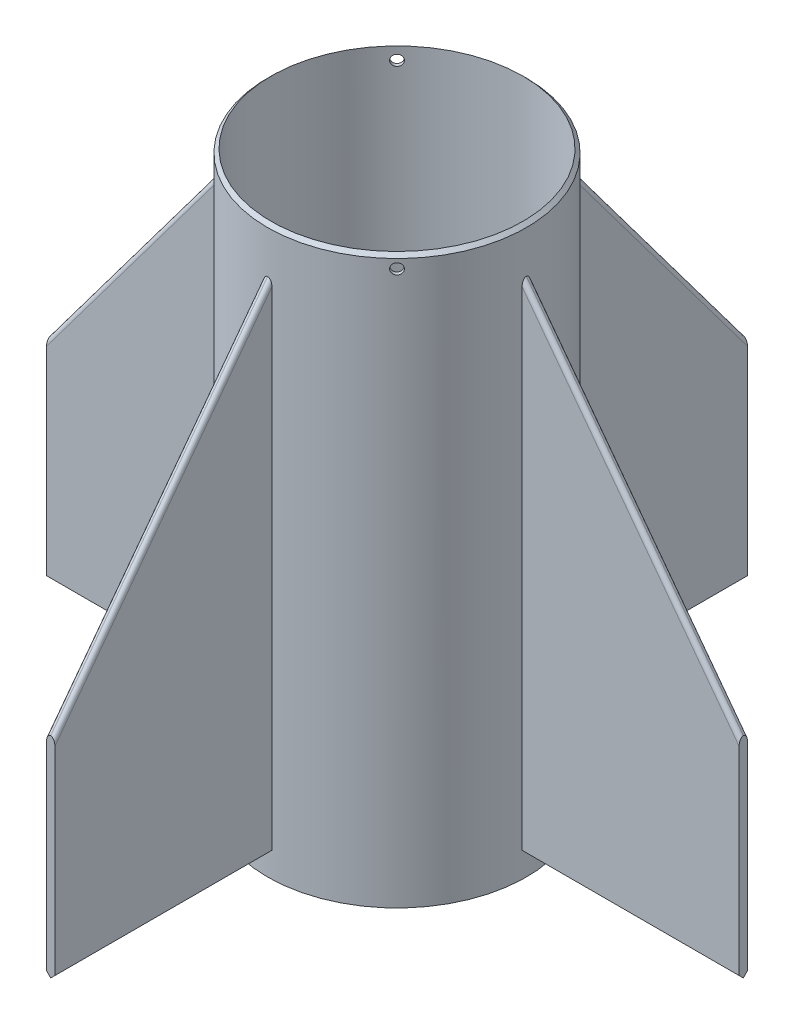
SolidWorks part; units mm, degrees
material "Thornel VCB-20 Carbon Cloth"
ref_plane "Front Plane" through (0, 0, 0) normal (0, 0, 1) x (1, 0, 0)
ref_plane "Top Plane" through (0, 0, 0) normal (0, 1, 0) x (1, 0, 0)
ref_plane "Right Plane" through (0, 0, 0) normal (1, 0, 0) x (0, 0, -1)
sketch "Sketch1" plane through (0, 0, 0) normal (0, 1, 0) x (1, 0, 0)
  circle A0 centre (0, 0) radius 76.2
  circle A1 centre (0, 0) radius 78.359
  dimension "D1" = 152.4
  dimension "D2" = 156.718
extrude "Boss-Extrude1" add sketch "Sketch1" along normal blind 342.9
sketch "Sketch2" plane through (0, 0, 0) normal (0, 0, 1) x (1, 0, 0)
  line L0 (76.2, 317.5) -> (76.2, 12.7)
  line L1 (76.2, 12.7) -> (209.55, 12.7)
  line L2 (209.55, 12.7) -> (209.55, 139.7)
  line L3 (209.55, 139.7) -> (76.2, 317.5)
  dimension "D1" = 76.2
  dimension "D2" = 127
  dimension "D3" = 133.35
  dimension "D4" = 304.8
  dimension "D5" = 177.8
  dimension "D6" = 12.7
extrude "Boss-Extrude2" add sketch "Sketch2" along normal blind 2.54 and the other way blind 2.54 separate body
sketch "Sketch3" plane through (0, 0, 0) normal (0, 0, 1) x (1, 0, 0)
  line L0 (0, -69.284) -> (0, 493.4849) construction
fillet "Fillet2" radius 2.54 2 edges at (142.875, 228.6, -2.54) (142.875, 228.6, 2.54)
chamfer "Chamfer2" distance 2.54 angle 45 2 edges at (142.875, 12.7, -2.54) (142.875, 12.7, 2.54)
pattern_circular "CirPattern1" count 4 over 360 about axis through (0, -69.284, 0) along (0, 1, 0) of bodies 102
ref_plane "Plane1" through (0, 0, 0) normal (-0.7071, 0, -0.7071) x (-0.7071, 0, 0.7071)
sketch "Sketch4" plane through (0, 0, 0) normal (-0.7071, 0, -0.7071) x (-0.7071, 0, 0.7071)
  line L0 (0, 342.9) -> (0, 0) construction
  circle A0 centre (0, 334.9498) radius 3.175
  dimension "D1" = 6.35
  dimension "D2" = 334.9498
extrude "Cut-Extrude1" cut sketch "Sketch4" against normal through all contours A0
pattern_circular "CirPattern2" count 4 over 360 about axis through (0, -69.284, 0) along (0, 1, 0) of "Cut-Extrude1" reverse direction yes
chamfer "Chamfer3" distance 2.54 angle 45 1 edges at (0, 342.9, 78.359)
